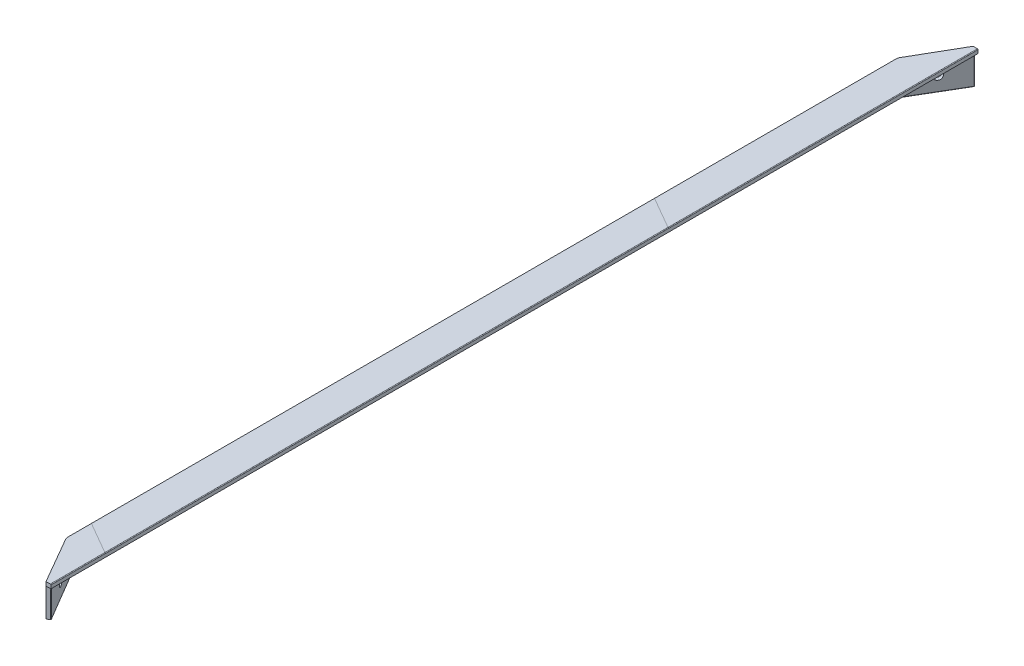
SolidWorks part; units mm, degrees
material "1.0116 (S235J2G3)"
ref_plane "Front Plane" through (0, 0, 0) normal (0, 0, 1) x (1, 0, 0)
ref_plane "Top Plane" through (0, 0, 0) normal (0, 1, 0) x (1, 0, 0)
ref_plane "Right Plane" through (0, 0, 0) normal (1, 0, 0) x (0, 0, -1)
sketch "Sketch1" plane through (0, 0, 0) normal (0, 0, 1) x (1, 0, 0)
  line L1 (44, 6) -> (44, 0)
  line L2 (44, 0) -> (0, 0)
  line L3 (0, 0) -> (0, -44)
  line L4 (0, -44) -> (-6, -44)
  line L6 (-6, -44) -> (-6, 6)
  line L7 (-6, 6) -> (44, 6)
  dimension "D1" = 0
  dimension "D2" = 6
  dimension "D3" = 6
  dimension "D4" = 6
  dimension "D5" = 50
  dimension "D6" = 50
  dimension "D7" = 0
extrude "Boss-Extrude1" add sketch "Sketch1" along normal blind 640
sketch "Sketch4" plane through (0, 0, 0) normal (0, 1, 0) x (1, 0, 0)
  line L0 (-6, -640) -> (36.5, -713.6122)
  line L1 (36.5, -713.6122) -> (44, -713.6122)
  line L2 (44, -713.6122) -> (44, -640)
  line L3 (44, -640) -> (-6, -640)
  line L4 (-6, -640) -> (-6, 0) construction
  dimension "D1" = 210
  dimension "D2" = 90
  dimension "D3" = 85
extrude "Boss-Extrude2" add sketch "Sketch4" along normal blind 6
sketch "Sketch5" plane through (0, 0, 0) normal (0, -1, 0) x (1, 0, 0)
  line L0 (-6, 640) -> (36.5, 713.6122)
  line L1 (36.5, 713.6122) -> (41.6962, 710.6122)
  line L3 (41.6962, 710.6122) -> (0, 640)
  line L4 (0, 640) -> (0, 0) construction
  line L5 (0, 640) -> (0, 0) construction
  line L6 (0, 640) -> (-6, 640)
  dimension "D1" = 6
extrude "Boss-Extrude3" add sketch "Sketch5" along normal blind 44
sketch "Sketch6" plane through (-280.2115, 0, 165.4636) normal (0.8611, 0, -0.5085) x (-0.5085, 0, -0.8611)
  line L0 (-551.0928, -44) -> (-633.0968, -44) construction
  line L1 (-633.0968, -44) -> (-633.0968, 0) construction
  circle A0 centre (-592.0968, -22) radius 6
  dimension "D1" = 12
  dimension "D2" = 22
  dimension "D3" = 41
extrude "Cut-Extrude1" cut sketch "Sketch6" against normal blind 6
mirror "Mirror4" about plane through (0, 0, 0) normal (0, 0, 1) of "Boss-Extrude2", "Cut-Extrude1", "Boss-Extrude3", "Boss-Extrude1"
fillet "Fillet1" radius 10 4 edges at (-6, -19, 640) (-6, -19, -640) (0, -22, -640) (0, -22, 640)
sketch "Sketch8" plane through (0, 6, 0) normal (0, 1, 0) x (1, 0, 0)
  line L0 (-6, -601.2046) -> (44, -630.0722)
  line L1 (-6, -637.3205) -> (-6, 637.3205) construction
  line L2 (44, -713.6122) -> (44, 713.6122) construction
  line L3 (44, -630.0722) -> (44, 236.7622)
  line L4 (44, 236.7622) -> (-6, 265.6297)
  line L5 (-6, 265.6297) -> (-6, -601.2046)
  line L6 (36.5, -713.6122) -> (44, -713.6122) construction
  dimension "D1" = 60
  dimension "D2" = 60
  dimension "D3" = 476.85
  dimension "D4" = 83.54
split line "Split Line1"
fillet "Fillet2" radius 4 5 edges at (21.5427, 0, 676.4824) (0.3535, 0, 639.9034) (21.5427, 0, -676.4824) (0.3535, 0, -639.9034) (0, 0, 0)
fillet "Fillet8" radius 1 17 edges at (44, 6, 671.8422) (44, 6, -475.1872) (44, 6, 196.655) (21.5427, -44, 676.4824) (0.3535, -44, 639.9034) (21.5427, -44, -676.4824) (0.3535, -44, -639.9034) (0, -44, 0) (15.9199, -44, 677.9663) (-5.6593, -44, 639.9087) (15.9199, -44, -677.9663) (-5.6593, -44, -639.9087) (-6, -44, 0) (42.4757, -1.2691, 710.1621) (41.6962, -23.917, 710.6122) (42.2178, -1.6937, -710.311) (41.6962, -23.917, -710.6122)
